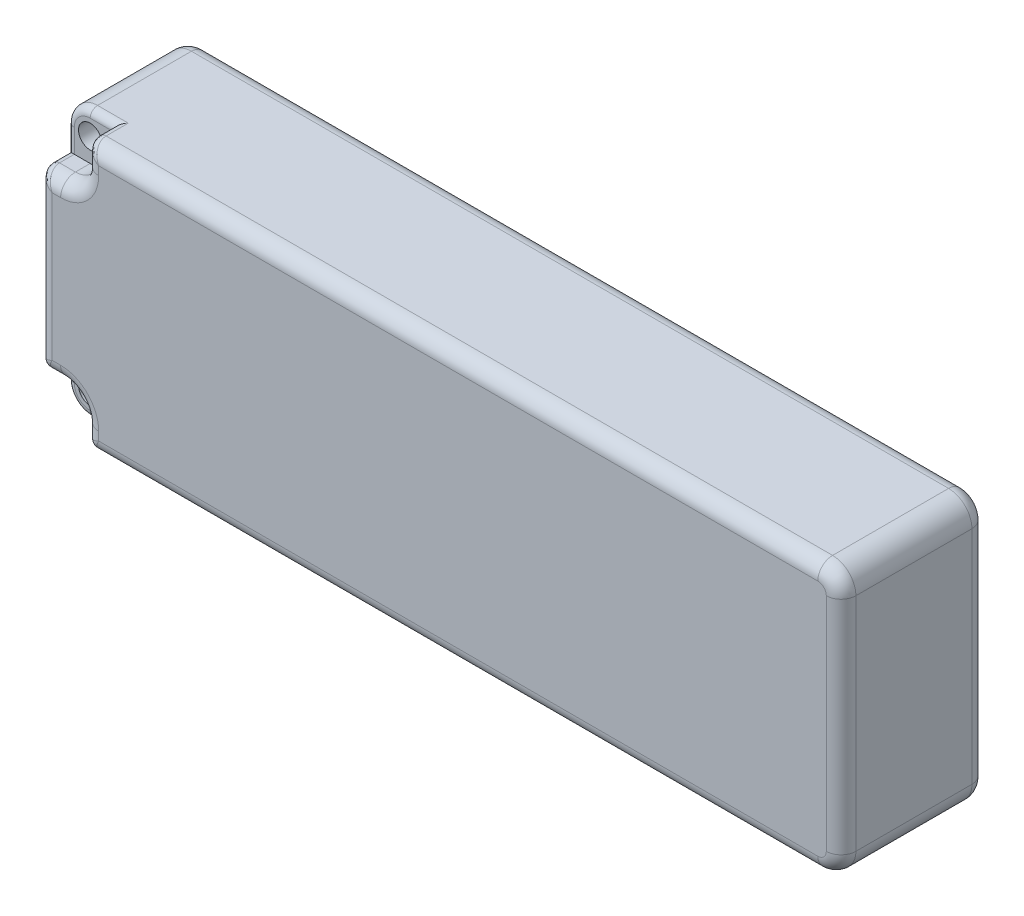
SolidWorks part; units mm, degrees
material "Custom Plastic"
ref_plane "Front Plane" through (0, 0, 0) normal (0, 0, 1) x (1, 0, 0)
ref_plane "Top Plane" through (0, 0, 0) normal (0, 1, 0) x (1, 0, 0)
ref_plane "Right Plane" through (0, 0, 0) normal (1, 0, 0) x (0, 0, -1)
sketch "Sketch1" plane through (0, 0, 0) normal (0, 0, 1) x (1, 0, 0)
  line L1 (-98.2277, 7.3577) -> (31.7723, 7.3577)
  line L2 (-102.2277, 3.3577) -> (-102.2277, -34.6423)
  line L3 (-98.2277, -38.6423) -> (31.7723, -38.6423)
  line L4 (35.7723, 3.3577) -> (35.7723, -34.6423)
  arc A0 (31.7723, -38.6423) -> (35.7723, -34.6423) centre (31.7723, -34.6423) ccw
  arc A1 (31.7723, 7.3577) -> (35.7723, 3.3577) centre (31.7723, 3.3577) cw
  arc A2 (-102.2277, -34.6423) -> (-98.2277, -38.6423) centre (-98.2277, -34.6423) ccw
  arc A3 (-98.2277, 7.3577) -> (-102.2277, 3.3577) centre (-98.2277, 3.3577) ccw
  point P6 (35.7723, -38.6423)
  point P9 (35.7723, 7.3577)
  point P14 (-102.2277, 7.3577)
  dimension "D3" = 4
  dimension "D1" = 138
  dimension "D2" = 46
extrude "Boss-Extrude1" add sketch "Sketch1" along normal blind 25
sketch "Sketch2" plane through (0, 0, 25) normal (0, 0, 1) x (1, 0, 0)
  line L0 (31.7723, 7.3577) -> (-98.2277, 7.3577) construction
  line L1 (-102.2277, 3.3577) -> (-102.2277, -34.6423) construction
  line L2 (-98.2277, -38.6423) -> (31.7723, -38.6423) construction
  line L3 (-102.2277, -30.6423) -> (-98.2277, -30.6423)
  line L4 (-94.2277, -34.6423) -> (-94.2277, -38.6423)
  line L5 (-102.2277, -0.6423) -> (-98.2277, -0.6423)
  line L6 (-94.2277, 3.3577) -> (-94.2277, 7.3577)
  line L7 (-102.2277, -0.6423) -> (-102.2277, 7.3577)
  line L8 (-102.2277, 7.3577) -> (-94.2277, 7.3577)
  line L9 (-102.2277, -30.6423) -> (-102.2277, -38.6423)
  line L10 (-102.2277, -38.6423) -> (-94.2277, -38.6423)
  circle A0 centre (-98.2277, 3.3577) radius 2
  circle A1 centre (-98.2277, -34.6423) radius 2
  arc A2 (-98.2277, -30.6423) -> (-94.2277, -34.6423) centre (-98.2277, -34.6423) cw
  arc A3 (-98.2277, -0.6423) -> (-94.2277, 3.3577) centre (-98.2277, 3.3577) ccw
  dimension "D2" = 4
  dimension "D4" = 4
  dimension "D7" = 4
  dimension "D8" = 4
  dimension "D11" = 4
  dimension "D1" = 4
  dimension "D3" = 4
  dimension "D5" = 4
  dimension "D6" = 4
  dimension "D9" = 4
  dimension "D10" = 4
  dimension "D12" = 4
  dimension "D13" = 4
extrude "Cut-Extrude1" cut sketch "Sketch2" against normal blind 5.08
sketch "Sketch6" plane through (0, 0, 25) normal (0, 0, 1) x (1, 0, 0)
  circle A0 centre (-98.2277, 3.3577) radius 2 construction
  circle A1 centre (-98.2277, -34.6423) radius 2 construction
  circle A2 centre (-98.2277, 3.3577) radius 2
  circle A3 centre (-98.2277, -34.6423) radius 2
extrude "Cut-Extrude2" cut sketch "Sketch6" against normal blind 12.7
fillet "Fillet1" radius 2.54 20 edges at (35.7723, -15.6423, 0) (34.6008, -37.4707, 0) (-33.2277, -38.6423, 0) (-101.0561, -37.4707, 0) (-102.2277, -15.6423, 0) (-101.0561, 6.1862, 0) (-33.2277, 7.3577, 0) (34.6008, 6.1862, 0) (-94.2277, 5.3577, 25) (-95.3992, 0.5293, 25) (-100.2277, -0.6423, 25) (-102.2277, -15.6423, 25) (-100.2277, -30.6423, 25) (-95.3992, -31.8138, 25) (-94.2277, -36.6423, 25) (-31.2277, -38.6423, 25) (34.6008, -37.4707, 25) (35.7723, -15.6423, 25) (34.6008, 6.1862, 25) (-31.2277, 7.3577, 25)
fillet "Fillet2" radius 1.27 14 edges at (-93.4837, 6.6138, 24.2561) (-101.4837, -1.3862, 24.2561) (-93.4837, -37.8983, 24.2561) (-101.4837, -29.8983, 24.2561) (-94.2277, 7.3577, 21.19) (-96.2277, 7.3577, 19.92) (-102.2277, 1.3577, 19.92) (-102.2277, -0.6423, 21.19) (-94.2277, -38.6423, 21.19) (-96.2277, -38.6423, 19.92) (-102.2277, -32.6423, 19.92) (-102.2277, -30.6423, 21.19) (-101.0561, 6.1862, 19.92) (-101.0561, -37.4707, 19.92)
